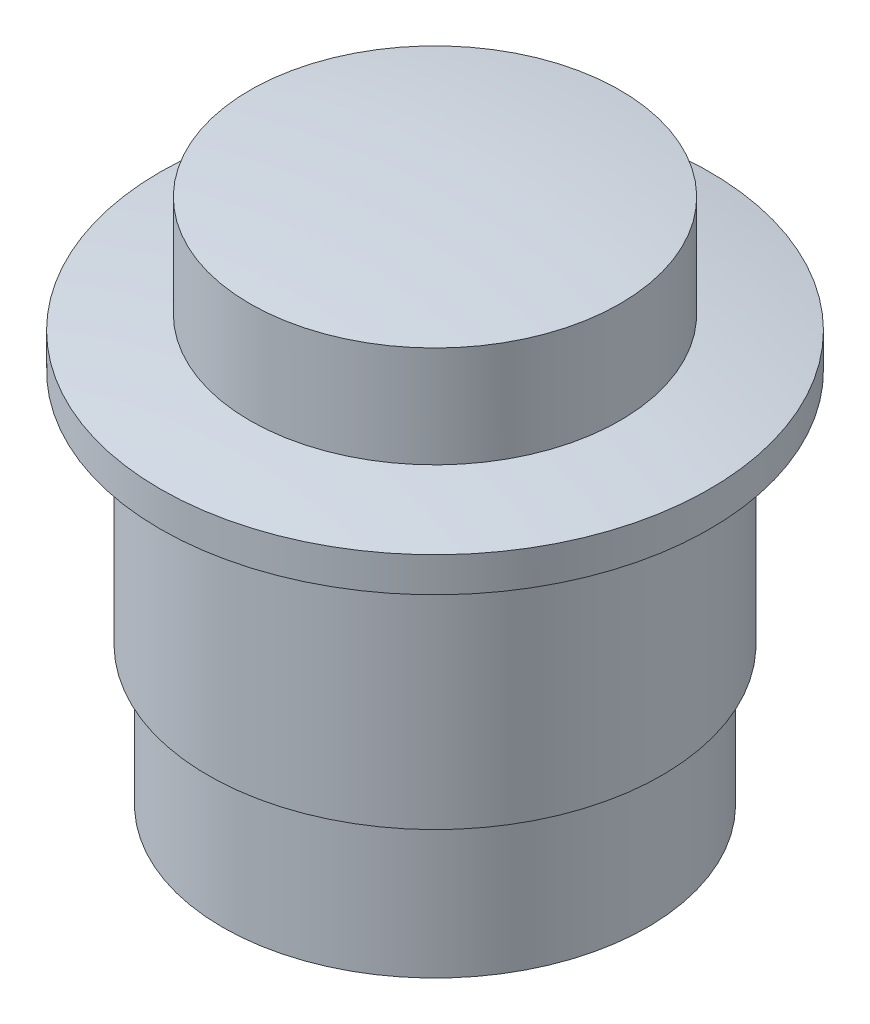
SolidWorks part; units mm, degrees
ref_plane "Front Plane" through (0, 0, 0) normal (0, 0, 1) x (1, 0, 0)
ref_plane "Top Plane" through (0, 0, 0) normal (0, 1, 0) x (1, 0, 0)
ref_plane "Right Plane" through (0, 0, 0) normal (1, 0, 0) x (0, 0, -1)
sketch "Sketch1" plane through (0, 0, 0) normal (0, 1, 0) x (1, 0, 0)
  circle A0 centre (0, 0) radius 7.35
  dimension "D1" = 14.7
extrude "Boss-Extrude1" add sketch "Sketch1" along normal blind 4.8
sketch "Sketch2" plane through (0, 4.8, 0) normal (0, 1, 0) x (1, 0, 0)
  circle A0 centre (0, 0) radius 7.85
  dimension "D1" = 15.7
extrude "Boss-Extrude2" add sketch "Sketch2" along normal offset from surface (8.2 mm away) 13 up to face at (0, 0, 7.35)
sketch "Sketch3" plane through (0, 0, 0) normal (0, 0, 1) x (1, 0, 0)
  line L0 (-7.85, 13) -> (-9.5, 13)
  line L1 (-9.5, 13) -> (-9.5, 14.2)
  line L2 (0, 15.2009) -> (0, -2.1066) construction
  line L3 (-6.4, 14.6995) -> (-6.4, 18.1995)
  line L4 (0, 18.6108) -> (0, 13)
  line L5 (7.85, 13) -> (-7.85, 13) construction
  line L6 (0, 13) -> (-7.85, 13)
  arc A0 (-6.4, 14.6995) -> (-9.5, 14.2) centre (0, -34.8892) ccw
  arc A1 (0, 18.6108) -> (-6.4, 18.1995) centre (0, -31.3892) ccw
  arc A2 (-49.9694, -33.1392) -> (49.9694, -33.1392) centre (0, -31.3892) ccw
  arc A3 (-49.9694, -33.1392) -> (49.9694, -33.1392) centre (0, -34.8892) ccw
  dimension "D3" = 100
  dimension "D1" = 19
  dimension "D2" = 1.2
  dimension "D4" = 12.8
  dimension "D5" = 3.5
revolve "Revolve2" add sketch "Sketch3" angle 360 about L2 region at (-3.7, 15.5089, 0)
